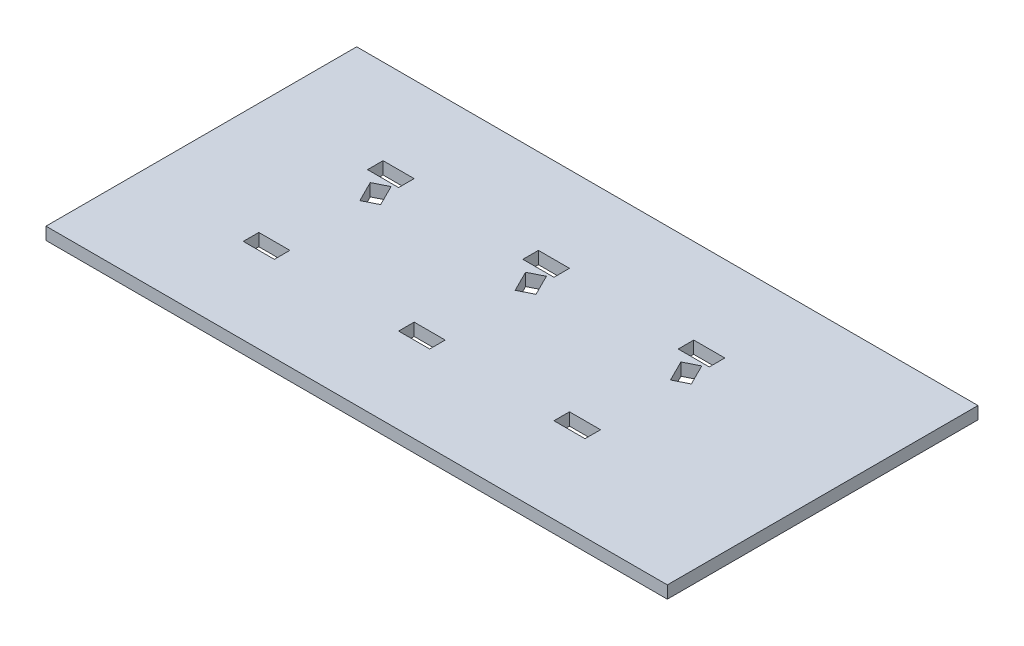
SolidWorks part; units mm, degrees
ref_plane "Front Plane" through (0, 0, 0) normal (0, 0, 1) x (1, 0, 0)
ref_plane "Top Plane" through (0, 0, 0) normal (0, 1, 0) x (1, 0, 0)
ref_plane "Right Plane" through (0, 0, 0) normal (1, 0, 0) x (0, 0, -1)
sketch "Sketch1" plane through (0, 0, 0) normal (0, 1, 0) x (1, 0, 0)
  line L1 (-50.8, -25.4) -> (50.8, -25.4)
  line L2 (-50.8, -25.4) -> (-50.8, 25.4)
  line L3 (-50.8, 25.4) -> (50.8, 25.4)
  line L4 (50.8, -25.4) -> (50.8, 25.4)
  line L5 (0, 25.4) -> (0, -25.4) construction
  line L6 (-50.8, 0) -> (50.8, 0) construction
  point P0 (0, 0)
  dimension "D1" = 50.8
  dimension "D2" = 101.6
extrude "Boss-Extrude1" add sketch "Sketch1" along normal blind 2.032
sketch "Sketch2" plane through (0, 2.032, 0) normal (0, 1, 0) x (1, 0, 0)
  line L0 (-3.3577, 3.8746) -> (-1.0859, 5.0107)
  line L1 (-3.3577, 3.8746) -> (-5.0618, 7.2822)
  line L2 (-1.0859, 5.0107) -> (-2.7901, 8.4183)
  line L3 (-5.0618, 7.2822) -> (-2.7901, 8.4183)
  line L5 (-1.1176, 0) -> (1.1176, 0) construction
  circle A0 centre (0, 0) radius 5.127 construction
  dimension "D1" = 10.254
  dimension "D3" = 3.81
  dimension "D4" = 2.54
  dimension "D2" = 63.43
extrude "Cut-Extrude1" cut sketch "Sketch2" against normal through all contours L3 L1 L0 L2 region at (-3.0739, 2.032, -6.1464)
sketch "Sketch3" plane through (0, 2.032, 0) normal (0, 1, 0) x (1, 0, 0)
  line L0 (-7.112, 8.89) -> (-2.032, 8.89)
  line L1 (-7.112, 8.89) -> (-7.112, 11.43)
  line L2 (-2.032, 8.89) -> (-2.032, 11.43)
  line L3 (-7.112, 11.43) -> (-2.032, 11.43)
  line L4 (-1.1176, 0) -> (1.1176, 0) construction
  line L5 (0, -1.1176) -> (0, 1.1176) construction
  dimension "D1" = 2.54
  dimension "D2" = 5.08
  dimension "D3" = 2.032
  dimension "D4" = 8.89
extrude "Cut-Extrude2" cut sketch "Sketch3" against normal through all
mirror "Mirror1" about plane through (0, 0, 0) normal (0, 0, 1) of "Cut-Extrude2"
pattern_linear "LPattern1" count 2 spacing 25.4 along (-1, 0, 0) count 2 spacing 25.4 along (1, 0, 0) of "Cut-Extrude1", "Cut-Extrude2", "Mirror1"
equation "\"Arrow Height\"= 1in"
equation "\"Button Height\"= 2in"
equation "\"Button Width\"= 4in"
equation "\"Haptic Diameter\"= 10mm"
equation "\"Haptic Thickness\"= 2.7mm"
equation "\"D1@Sketch1\"=\"Button Height\""
equation "\"D2@Sketch1\"=\"Button Width\""
equation "\"D1@Sketch2\"=\"Haptic Diameter\"+.01in"
equation "\"Arrow Spacing\"= 1in"
equation "\"Arrow Width\"= 0.75in"
equation "\"Haptic Wire Angle\"= 63.43"
equation "\"Haptic Wire Width\"= .1in"
equation "\"Hatic Wire Height\"= .15in"
equation "\"D2@Sketch2\"=\"Haptic Wire Angle\""
equation "\"D4@Sketch2\"=\"Haptic Wire Width\""
equation "\"D3@Sketch2\"=\"Hatic Wire Height\""
